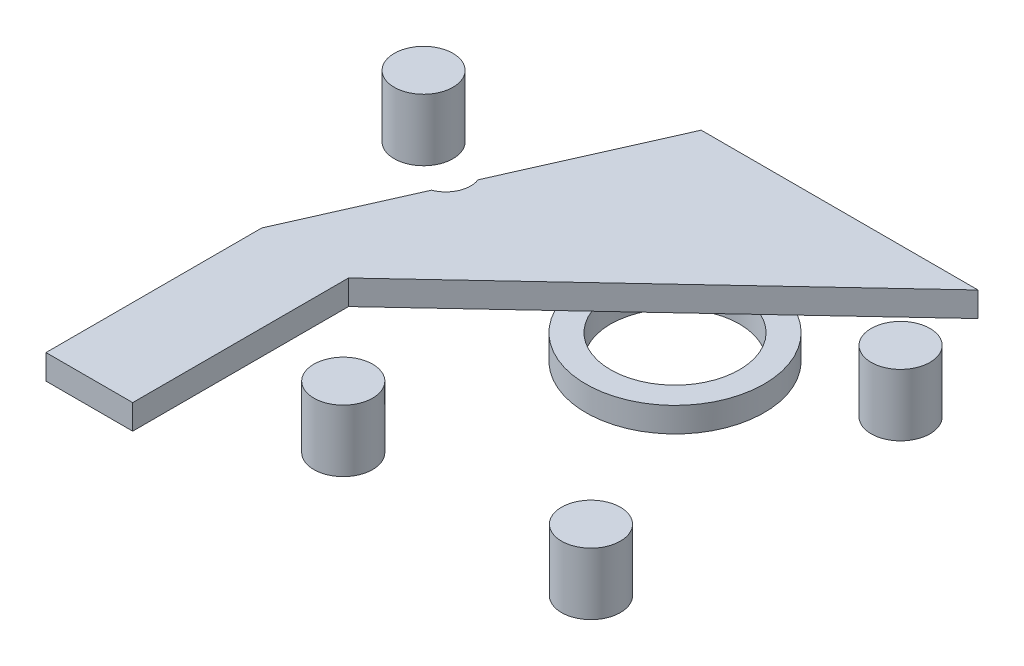
SolidWorks part; units mm, degrees
ref_plane "Front Plane" through (0, 0, 0) normal (0, 0, 1) x (1, 0, 0)
ref_plane "Top Plane" through (0, 0, 0) normal (0, 1, 0) x (1, 0, 0)
ref_plane "Right Plane" through (0, 0, 0) normal (1, 0, 0) x (0, 0, -1)
sketch "Sketch1" plane through (0, 0, 0) normal (0, 1, 0) x (1, 0, 0)
  line L6 (-3.5, 8.7143) -> (-3.5, -8.7143)
  line L7 (-3.5, -8.7143) -> (3.5, -8.7143)
  line L8 (3.5, 8.7143) -> (3.5, -8.7143)
  line L9 (-3.5, -8.7143) -> (3.5, -8.7143) construction
  line L10 (40.5, -8.7143) -> (40.5, 8.7143) construction
  line L11 (-3.5, 8.7143) -> (7.4, 33.2857)
  line L12 (7.4, 33.2857) -> (29.75, 33.2857)
  line L13 (29.75, 33.2857) -> (3.5, 8.7143)
  point P4 (0, -8.7143)
  point P5 (3.5, 0)
extrude "Boss-Extrude1" add sketch "Sketch1" along normal blind 2
sketch "Sketch3" plane through (0, 0, 0) normal (0, -1, 0) x (1, 0, 0)
  line L0 (8.5, -3.2857) -> (28.5, -3.2857) construction
  line L1 (-9.9916, -28.2645) -> (28.5, -28.2857) construction
  circle A0 centre (8.5, -3.2857) radius 2.375
  circle A1 centre (-9.9916, -28.2645) radius 2.3728
  circle A2 centre (28.5, -28.2857) radius 2.375
  circle A3 centre (28.5, -3.2857) radius 2.375
  dimension "D1" = 4.7457
  dimension "D2" = 4.75
  dimension "D3" = 4.75
  dimension "D4" = 4.75
extrude "Boss-Extrude3" add sketch "Sketch3" along normal blind 5
sketch "Sketch4" plane through (0, 0, 0) normal (0, -1, 0) x (1, 0, 0)
  circle A0 centre (18.5, -20.0735) radius 5.2
  circle A1 centre (18.5, -20.0735) radius 7.2
  dimension "D1" = 10.4
  dimension "D2" = 2
extrude "Boss-Extrude4" add sketch "Sketch4" along normal blind 2
sketch "Sketch5" plane through (0, 2, 0) normal (0, 1, 0) x (1, 0, 0)
  circle A0 centre (18.5, 20.0735) radius 1.25
  dimension "D1" = 2.5
extrude "Cut-Extrude1" cut sketch "Sketch5" against normal blind 2 rebuild error yes
sketch "Sketch6" plane through (0, 2, 0) normal (0, 1, 0) x (1, 0, 0)
  circle A0 centre (0, 20.0735) radius 2
  dimension "D1" = 4
extrude "Cut-Extrude2" cut sketch "Sketch6" against normal blind 1
